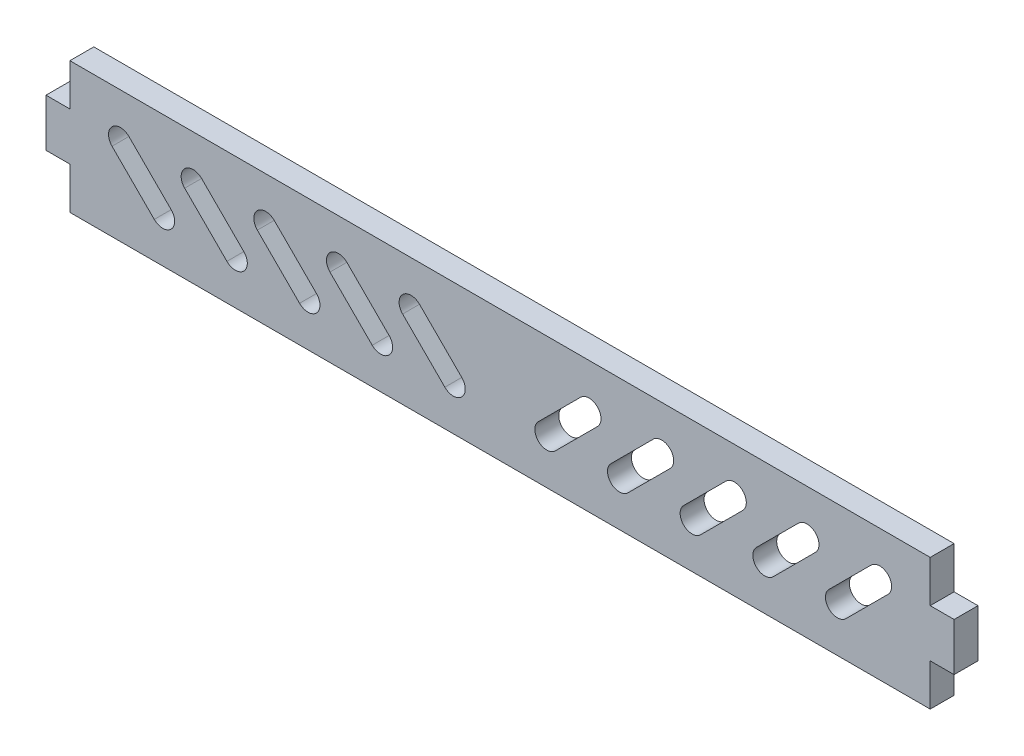
SolidWorks part; units mm, degrees
ref_plane "Front Plane" through (0, 0, 0) normal (0, 0, 1) x (1, 0, 0)
ref_plane "Top Plane" through (0, 0, 0) normal (0, 1, 0) x (1, 0, 0)
ref_plane "Right Plane" through (0, 0, 0) normal (1, 0, 0) x (0, 0, -1)
sketch "Sketch1" plane through (0, 0, 0) normal (0, 0, 1) x (1, 0, 0)
  line L0 (-114.3, 8.7301) -> (0, 8.7301) construction
  line L1 (0, 0) -> (-114.3, 0)
  line L2 (0, 0) -> (0, 5.5551)
  line L3 (0, 17.4602) -> (-114.3, 17.4602)
  line L4 (-114.3, 0) -> (-114.3, 5.5551)
  line L5 (3.175, 11.9051) -> (0, 11.9051)
  line L6 (-57.15, 17.4602) -> (-57.15, 0) construction
  line L7 (3.175, 5.5551) -> (0, 5.5551)
  line L8 (-117.475, 5.5551) -> (-114.3, 5.5551)
  line L9 (0, 11.9051) -> (0, 17.4602)
  line L13 (-114.3, 11.9051) -> (-114.3, 17.4602)
  line L14 (0, 5.5551) -> (0, 11.9051) construction
  line L15 (3.175, 11.9051) -> (3.175, 5.5551)
  line L16 (-117.475, 11.9051) -> (-117.475, 5.5551)
  line L17 (-117.475, 11.9051) -> (-114.3, 11.9051)
  point P9 (-3.175, 8.7301)
  dimension "D1" = 114.3
  dimension "D2" = 17.4602
extrude "Boss-Extrude1" add sketch "Sketch1" along normal blind 3.175
sketch "Sketch2" plane through (0, 0, 3.175) normal (0, 0, 1) x (1, 0, 0)
  line L0 (-57.15, 17.4602) -> (-57.15, 0) construction
  line L1 (0, 17.4602) -> (-114.3, 17.4602) construction
  line L2 (-114.3, 0) -> (0, 0) construction
  line L3 (-107.5813, 11.5364) -> (-101.9687, 5.9238) construction
  line L4 (-106.4588, 12.659) -> (-100.8461, 7.0463)
  line L5 (-108.7039, 10.4139) -> (-103.0912, 4.8012)
  line L6 (-117.475, 8.7301) -> (3.175, 8.7301) construction
  line L7 (-117.475, 11.9051) -> (-117.475, 5.5551) construction
  line L8 (3.175, 5.5551) -> (3.175, 11.9051) construction
  line L9 (-114.3, 17.4602) -> (-114.3, 11.9051) construction
  line L10 (-97.9293, 11.5364) -> (-92.3167, 5.9238) construction
  line L11 (-96.8068, 12.659) -> (-91.1941, 7.0463)
  line L12 (-99.0519, 10.4139) -> (-93.4392, 4.8012)
  line L13 (-88.2773, 11.5364) -> (-82.6647, 5.9238) construction
  line L14 (-87.1548, 12.659) -> (-81.5421, 7.0463)
  line L15 (-89.3999, 10.4139) -> (-83.7872, 4.8012)
  line L16 (-78.6253, 11.5364) -> (-73.0127, 5.9238) construction
  line L17 (-77.5028, 12.659) -> (-71.8901, 7.0463)
  line L18 (-79.7479, 10.4139) -> (-74.1352, 4.8012)
  line L19 (-68.9733, 11.5364) -> (-63.3607, 5.9238) construction
  line L20 (-67.8508, 12.659) -> (-62.2381, 7.0463)
  line L21 (-70.0959, 10.4139) -> (-64.4832, 4.8012)
  line L22 (-45.3267, 11.5364) -> (-50.9393, 5.9238) construction
  line L23 (-46.4492, 12.659) -> (-52.0619, 7.0463)
  line L24 (-44.2041, 10.4139) -> (-49.8168, 4.8012)
  line L25 (-35.6747, 11.5364) -> (-41.2873, 5.9238) construction
  line L26 (-36.7972, 12.659) -> (-42.4099, 7.0463)
  line L27 (-34.5521, 10.4139) -> (-40.1648, 4.8012)
  line L28 (-26.0227, 11.5364) -> (-31.6353, 5.9238) construction
  line L29 (-27.1452, 12.659) -> (-32.7579, 7.0463)
  line L30 (-24.9001, 10.4139) -> (-30.5128, 4.8012)
  line L31 (-16.3707, 11.5364) -> (-21.9833, 5.9238) construction
  line L32 (-17.4932, 12.659) -> (-23.1059, 7.0463)
  line L33 (-15.2481, 10.4139) -> (-20.8608, 4.8012)
  line L34 (-6.7187, 11.5364) -> (-12.3313, 5.9238) construction
  line L35 (-7.8412, 12.659) -> (-13.4539, 7.0463)
  line L36 (-5.5961, 10.4139) -> (-11.2088, 4.8012)
  arc A0 (-106.4588, 12.659) -> (-108.7039, 10.4139) centre (-107.5813, 11.5364) ccw
  arc A1 (-103.0912, 4.8012) -> (-100.8461, 7.0463) centre (-101.9687, 5.9238) ccw
  arc A2 (-96.8068, 12.659) -> (-99.0519, 10.4139) centre (-97.9293, 11.5364) ccw
  arc A3 (-93.4392, 4.8012) -> (-91.1941, 7.0463) centre (-92.3167, 5.9238) ccw
  arc A4 (-87.1548, 12.659) -> (-89.3999, 10.4139) centre (-88.2773, 11.5364) ccw
  arc A5 (-83.7872, 4.8012) -> (-81.5421, 7.0463) centre (-82.6647, 5.9238) ccw
  arc A6 (-77.5028, 12.659) -> (-79.7479, 10.4139) centre (-78.6253, 11.5364) ccw
  arc A7 (-74.1352, 4.8012) -> (-71.8901, 7.0463) centre (-73.0127, 5.9238) ccw
  arc A8 (-67.8508, 12.659) -> (-70.0959, 10.4139) centre (-68.9733, 11.5364) ccw
  arc A9 (-64.4832, 4.8012) -> (-62.2381, 7.0463) centre (-63.3607, 5.9238) ccw
  arc A10 (-46.4492, 12.659) -> (-44.2041, 10.4139) centre (-45.3267, 11.5364) cw
  arc A11 (-49.8168, 4.8012) -> (-52.0619, 7.0463) centre (-50.9393, 5.9238) cw
  arc A12 (-36.7972, 12.659) -> (-34.5521, 10.4139) centre (-35.6747, 11.5364) cw
  arc A13 (-40.1648, 4.8012) -> (-42.4099, 7.0463) centre (-41.2873, 5.9238) cw
  arc A14 (-27.1452, 12.659) -> (-24.9001, 10.4139) centre (-26.0227, 11.5364) cw
  arc A15 (-30.5128, 4.8012) -> (-32.7579, 7.0463) centre (-31.6353, 5.9238) cw
  arc A16 (-17.4932, 12.659) -> (-15.2481, 10.4139) centre (-16.3707, 11.5364) cw
  arc A17 (-20.8608, 4.8012) -> (-23.1059, 7.0463) centre (-21.9833, 5.9238) cw
  arc A18 (-7.8412, 12.659) -> (-5.5961, 10.4139) centre (-6.7187, 11.5364) cw
  arc A19 (-11.2088, 4.8012) -> (-13.4539, 7.0463) centre (-12.3313, 5.9238) cw
  point P8 (-104.775, 8.7301)
  point P19 (-114.3, 14.6827)
  point P26 (-95.123, 8.7301)
  point P33 (-85.471, 8.7301)
  point P40 (-75.819, 8.7301)
  point P47 (-66.167, 8.7301)
  point P52 (-48.133, 8.7301)
  point P59 (-38.481, 8.7301)
  point P66 (-28.829, 8.7301)
  point P73 (-19.177, 8.7301)
  point P80 (-9.525, 8.7301)
  dimension "D1" = 7.9375
  dimension "D2" = 3.175
  dimension "D3" = 9.525
  dimension "D4" = 5
extrude "Cut-Extrude1" cut sketch "Sketch2" against normal through all
